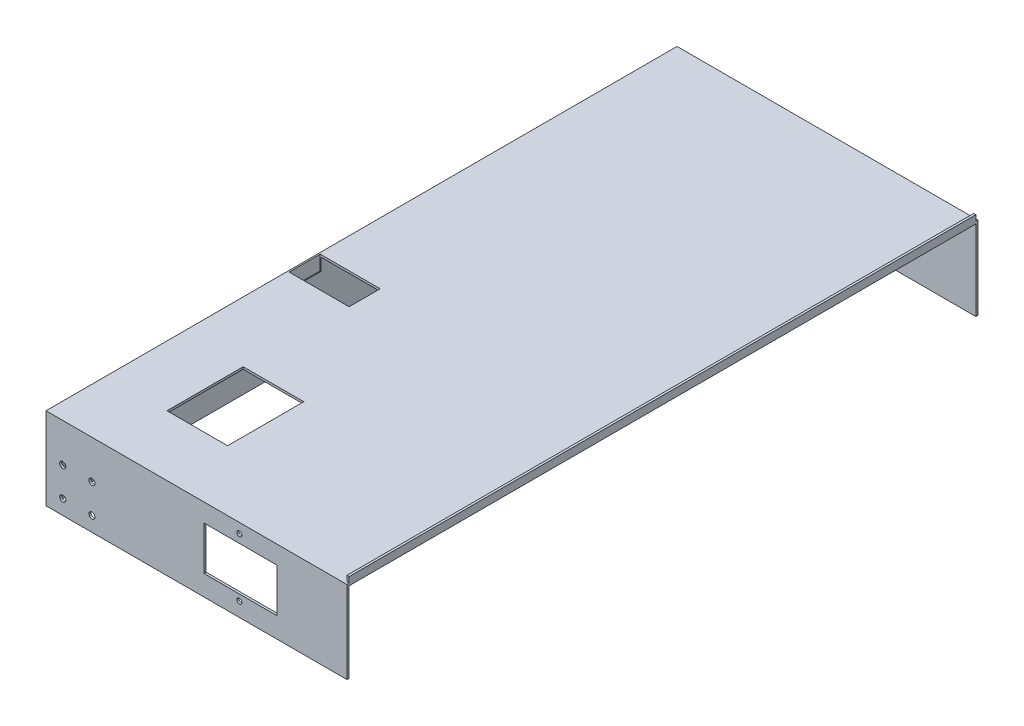
SolidWorks part; units mm, degrees
ref_plane "Front Plane" through (0, 0, 0) normal (0, 0, 1) x (1, 0, 0)
ref_plane "Top Plane" through (0, 0, 0) normal (0, 1, 0) x (1, 0, 0)
ref_plane "Right Plane" through (0, 0, 0) normal (1, 0, 0) x (0, 0, -1)
sketch "Sketch4" plane through (0, 0, 0) normal (0, 1, 0) x (1, 0, 0)
  line L0 (139.3737, 430) -> (344.3737, 430)
  line L1 (344.3737, 430) -> (344.3737, 0)
  line L2 (344.3737, 0) -> (139.3737, 0)
  line L3 (139.3737, 0) -> (139.3737, 65)
  line L7 (139.3737, 230) -> (139.3737, 430)
  line L8 (139.3737, 230) -> (139.3737, 65)
  line L10 (179.3737, 40) -> (220.958, 40)
  line L11 (179.3737, 40) -> (179.3737, 92.3012)
  line L12 (179.3737, 92.3012) -> (220.958, 92.3012)
  line L13 (220.958, 40) -> (220.958, 92.3012)
  dimension "D2" = 200
  dimension "D5" = 205
  dimension "D6" = 205
extrude "Boss-Extrude4" add sketch "Sketch4" along normal blind 1.5 separate body
sketch "Sketch5" plane through (0, 0, 0) normal (0, 0, 1) x (1, 0, 0)
  line L1 (139.3737, 1.5) -> (344.3737, 1.5)
  line L2 (139.3737, 1.5) -> (139.3737, -55)
  line L3 (139.3737, -55) -> (344.3737, -55)
  line L4 (344.3737, 1.5) -> (344.3737, -55)
  dimension "D1" = 56.5
sketch "Sketch7" plane through (0, 0, -430) normal (0, 0, -1) x (-1, 0, 0)
  line L1 (-139.3737, 1.5) -> (-344.3737, 1.5)
  line L2 (-139.3737, 1.5) -> (-139.3737, -55)
  line L3 (-139.3737, -55) -> (-344.3737, -55)
  line L4 (-344.3737, 1.5) -> (-344.3737, -55)
  dimension "D1" = 56.5
sketch "Sketch8" plane through (0, 1.5, 0) normal (0, 1, 0) x (1, 0, 0)
  line L0 (139.3737, 430) -> (344.3737, 430) construction
  line L1 (344.3737, 0) -> (342.8737, 0)
  line L2 (344.3737, 0) -> (344.3737, 430)
  line L3 (344.3737, 430) -> (342.8737, 430)
  line L4 (342.8737, 0) -> (342.8737, 430)
  dimension "D1" = 1.5
extrude "Boss-Extrude5" add sketch "Sketch5" along normal blind 1.5
extrude "Boss-Extrude14" add sketch "Sketch8" along normal blind 4
extrude "Boss-Extrude18" add sketch "Sketch7" along normal blind 1.5
sketch "Sketch9" plane through (139.3737, 0, 0) normal (-1, 0, 0) x (0, 0, 1)
  line L1 (-431.5, 1.5) -> (1.5, 1.5)
  line L2 (-431.5, 1.5) -> (-431.5, -55)
  line L3 (-431.5, -55) -> (1.5, -55)
  line L4 (1.5, 1.5) -> (1.5, -55)
extrude "Boss-Extrude19" add sketch "Sketch9" along normal blind 1.5
sketch "Sketch10" plane through (0, 0, 1.5) normal (0, 0, 1) x (1, 0, 0)
  circle A0 centre (169.3737, -45) radius 2.1
sketch "Sketch11" plane through (0, 0, 1.5) normal (0, 0, 1) x (1, 0, 0)
  line L1 (137.8737, -55) -> (137.8737, 1.5) construction
  line L2 (139.3737, -55) -> (344.3737, -55) construction
  circle A0 centre (149.3737, -45) radius 2.1
  dimension "D1" = 11.5
  dimension "D2" = 10
sketch "Sketch12" plane through (0, 0, 1.5) normal (0, 0, 1) x (1, 0, 0)
  line L0 (137.8737, -55) -> (137.8737, 1.5) construction
  line L1 (139.3737, 1.5) -> (344.3737, 1.5) construction
  circle A0 centre (149.3737, -25) radius 2.1
  dimension "D1" = 11.5
  dimension "D2" = 26.5
sketch "Sketch14" plane through (0, 0, 1.5) normal (0, 0, 1) x (1, 0, 0)
  line L0 (137.8737, -55) -> (137.8737, 1.5) construction
  line L1 (139.3737, 1.5) -> (344.3737, 1.5) construction
  circle A0 centre (169.3737, -25) radius 2.1
  dimension "D1" = 31.5
  dimension "D2" = 26.5
sketch "Sketch15" plane through (0, 0, -431.5) normal (0, 0, -1) x (-1, 0, 0)
  circle A0 centre (-169.3737, -25) radius 2.1
  circle A1 centre (-149.3737, -25) radius 2.1
  circle A2 centre (-169.3737, -45) radius 2.1
  circle A3 centre (-149.3737, -45) radius 2.1
extrude "Cut-Extrude1" cut sketch "Sketch15" against normal blind 10
extrude "Cut-Extrude2" cut sketch "Sketch14" against normal blind 10
extrude "Cut-Extrude3" cut sketch "Sketch12" against normal blind 10
extrude "Cut-Extrude4" cut sketch "Sketch10" against normal blind 10
extrude "Cut-Extrude5" cut sketch "Sketch11" against normal blind 10
sketch "Sketch17" plane through (0, 1.5, 0) normal (0, 1, 0) x (1, 0, 0)
  line L1 (138.8371, 185.641) -> (180.0505, 185.641)
  line L2 (138.8371, 185.641) -> (138.8371, 164.3117)
  line L3 (138.8371, 164.3117) -> (180.0505, 164.3117)
  line L4 (180.0505, 185.641) -> (180.0505, 164.3117)
extrude "Cut-Extrude6" cut sketch "Sketch17" against normal blind 10
sketch "Sketch18" plane through (0, 0, 1.5) normal (0, 0, 1) x (1, 0, 0)
  line L0 (139.3737, -55) -> (344.3737, -55) construction
  line L1 (246.3048, -11) -> (296.3048, -11)
  line L2 (246.3048, -11) -> (246.3048, -41)
  line L3 (246.3048, -41) -> (296.3048, -41)
  line L4 (296.3048, -11) -> (296.3048, -41)
  dimension "D1" = 14
sketch "Sketch19" plane through (0, 0, 1.5) normal (0, 0, 1) x (1, 0, 0)
  circle A0 centre (270.5434, -5.2715) radius 1.75
  circle A1 centre (270.5434, -45.2715) radius 1.75
  dimension "D1" = 3.5
extrude "Cut-Extrude7" cut sketch "Sketch18" against normal blind 10
extrude "Cut-Extrude8" cut sketch "Sketch19" against normal blind 10
ref_plane "Plane5" through (296.3048, -41, 1.5) normal (1, 0, 0) x (0, 0, -1)
